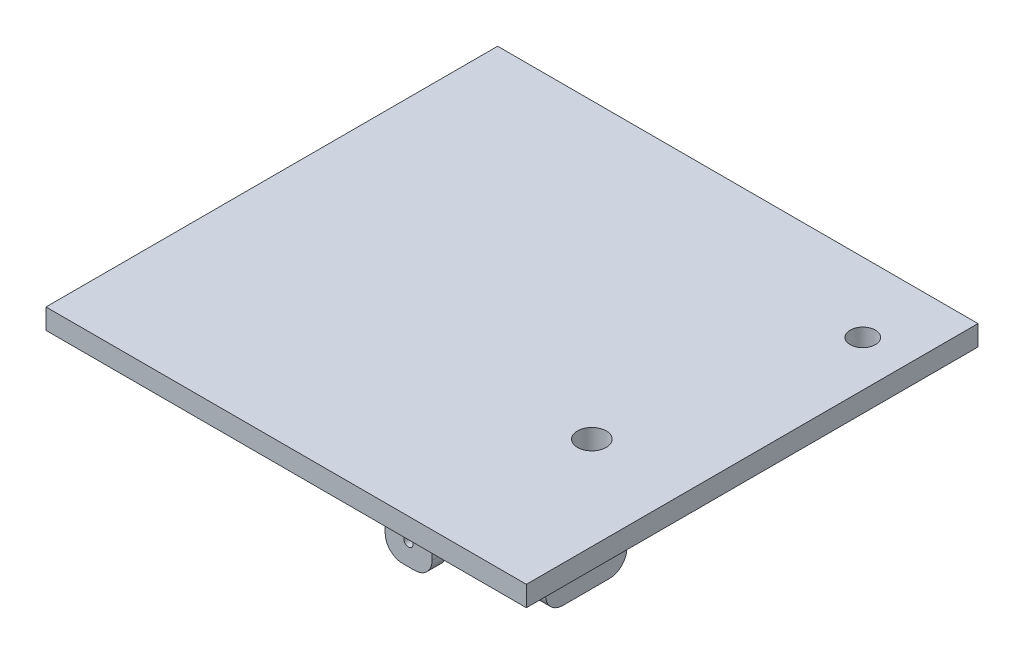
SolidWorks part; units mm, degrees
ref_plane "Front Plane" through (0, 0, 0) normal (0, 0, 1) x (1, 0, 0)
ref_plane "Top Plane" through (0, 0, 0) normal (0, 1, 0) x (1, 0, 0)
ref_plane "Right Plane" through (0, 0, 0) normal (1, 0, 0) x (0, 0, -1)
sketch "Sketch2" plane through (0, 0, 0) normal (0, 1, 0) x (1, 0, 0)
  line L0 (0, 0) -> (0, 77.75)
  line L1 (0, 77.75) -> (82.7, 77.75)
  line L2 (82.7, 77.75) -> (82.7, 0)
  line L3 (82.7, 0) -> (0, 0)
  dimension "D1" = 77.75
  dimension "D2" = 82.7
extrude "Boss-Extrude1" add sketch "Sketch2" along normal blind 3.5
sketch "Sketch3" plane through (0, 3.5, 0) normal (0, 1, 0) x (1, 0, 0)
  line L0 (54.7, 73.05) -> (44.7, 73.05)
  line L1 (44.7, 73.05) -> (44.7, 70.55)
  line L2 (44.7, 70.55) -> (54.7, 70.55)
  line L3 (54.7, 70.55) -> (54.7, 73.05)
  line L4 (82.7, 77.75) -> (0, 77.75) construction
  line L5 (82.7, 0) -> (82.7, 77.75) construction
  line L6 (61.77, 4.7) -> (51.7, 4.7)
  line L7 (51.7, 4.7) -> (51.7, 7.2)
  line L8 (51.7, 7.2) -> (61.77, 7.2)
  line L9 (61.77, 7.2) -> (61.77, 4.7)
  line L10 (0, 0) -> (82.7, 0) construction
  line L11 (75.5, 8) -> (75.5, 22)
  line L12 (75.5, 22) -> (78, 22)
  line L13 (78, 22) -> (78, 8)
  line L14 (78, 8) -> (75.5, 8)
  point P6 (54.7, 71.8)
  dimension "D1" = 4.7
  dimension "D2" = 28
  dimension "D3" = 38
  dimension "D4" = 4.7
  dimension "D5" = 2.5
  dimension "D6" = 2.5
  dimension "D7" = 31
  dimension "D8" = 20.93
  dimension "D9" = 4.7
  dimension "D10" = 2.5
  dimension "D11" = 8
  dimension "D12" = 22
extrude "Boss-Extrude2" add sketch "Sketch3" against normal blind 12.25
sketch "Sketch4" plane through (0, 0, 0) normal (0, -1, 0) x (1, 0, 0)
  line L0 (60.7, -29.75) -> (72.7, -29.75) construction
  line L1 (82.7, -77.75) -> (0, -77.75) construction
  line L3 (62.7, -30.275) -> (62.7, -24.275)
  line L4 (62.7, -30.275) -> (70.7, -30.275)
  line L5 (70.7, -30.275) -> (70.7, -24.275)
  line L7 (70.7, -24.275) -> (62.7, -24.275)
  line L8 (3.65, -5) -> (3.65, -72.75)
  line L9 (3.65, -72.75) -> (5.65, -72.75)
  line L10 (5.65, -72.75) -> (5.65, -5)
  line L11 (5.65, -5) -> (3.65, -5)
  line L12 (0, -77.75) -> (0, 0) construction
  line L13 (0, 0) -> (82.7, 0) construction
  line L14 (82.7, 0) -> (82.7, -77.75) construction
  circle A1 centre (66.7, -27.275) radius 2.475
  dimension "D2" = 48
  dimension "D3" = 20
  dimension "D4" = 4
  dimension "D5" = 4
  dimension "D6" = 53.475
  dimension "D8" = 3
  dimension "D10" = 2
  dimension "D11" = 3.65
  dimension "D12" = 5
  dimension "D13" = 5
extrude "Boss-Extrude3" add sketch "Sketch4" along normal blind 2.3 contours L4 L5 L7 L3
draft "Draft1" type of draft neutral plane draft angle 50 faces to draft 4 face at (70.7, -1.15, -27.275) face at (62.7, -1.15, -27.275) face at (66.7, -1.15, -24.275) face at (66.7, -1.15, -30.275) neutral plane through (0, -2.3, 0) neutral plane normal (0, -1, 0) parameters "D1"=50
extrude "Cut-Extrude1" cut sketch "Sketch4<3>" against normal up to surface and the other way up to surface contours A1 up to face at (41.35, 3.5, -38.875) other way up to face at (66.7, -2.3, -27.275)
sketch "Sketch4<3>" plane through (0, 0, 0) normal (0, -1, 0) x (1, 0, 0) same geometry as "Sketch4"
extrude "Boss-Extrude4" add sketch "Sketch4<4>" along normal blind 4 contours L10 L11 L8 L9
sketch "Sketch4<4>" plane through (0, 0, 0) normal (0, -1, 0) x (1, 0, 0) same geometry as "Sketch4"
sketch "Sketch5" plane through (0, 0, 0) normal (0, -1, 0) x (1, 0, 0)
  line L0 (82.7, -77.75) -> (0, -77.75) construction
  line L3 (82.7, 0) -> (82.7, -77.75) construction
  circle A0 centre (74.84, -65.77) radius 2.175
  dimension "D1" = 4.35
  dimension "D2" = 11.98
  dimension "D3" = 7.86
extrude "Cut-Extrude2" cut sketch "Sketch5" against normal up to surface (3.5 mm away) up to face at (66.7, 3.5, -29.75)
sketch "Sketch6" plane through (0, 0, -4.7) normal (0, 0, 1) x (1, 0, 0)
  line L0 (0, 0) -> (82.7, 0) construction
  line L1 (82.7, 3.5) -> (82.7, 0) construction
  circle A0 centre (57.7, -5) radius 0.8
  dimension "D1" = 1.6
  dimension "D2" = 5
  dimension "D3" = 25
extrude "Cut-Extrude3" cut sketch "Sketch6" against normal up to surface (2.5 mm away) up to face at (56.735, -4.375, -7.2)
sketch "Sketch7" plane through (0, 0, -73.05) normal (0, 0, -1) x (-1, 0, 0)
  line L0 (-82.7, 0) -> (0, 0) construction
  line L1 (-82.7, 3.5) -> (-82.7, 0) construction
  circle A0 centre (-49.7, -5) radius 0.8
  point P6 (-82.7, 1.75)
  dimension "D2" = 1.6
  dimension "D1" = 5
  dimension "D3" = 33
extrude "Cut-Extrude4" cut sketch "Sketch7" against normal up to surface (2.5 mm away) up to face at (49.7, -4.375, -70.55)
sketch "Sketch9" plane through (0, 0, -4.7) normal (0, 0, 1) x (1, 0, 0)
  line L0 (53.7, 0) -> (53.7, -8.75)
  line L1 (61.77, 0) -> (51.7, 0) construction
  line L2 (51.7, -8.75) -> (61.77, -8.75) construction
  line L3 (53.7, -8.75) -> (51.7, -8.75)
  line L4 (51.7, -8.75) -> (51.7, 0)
  line L5 (51.7, 0) -> (53.7, 0)
  dimension "D1" = 2
extrude "Cut-Extrude5" cut sketch "Sketch9" against normal blind 4
fillet "Fillet1" radius 5 2 edges at (54.7, -8.75, -71.8) (44.7, -8.75, -71.8)
fillet "Fillet4" radius 1 1 edges at (5.65, 0, -38.875)
fillet "Fillet5" radius 0.5 1 edges at (5.65, -4, -38.875)
sketch "Sketch10" plane through (78, 0, 0) normal (1, 0, 0) x (0, 0, -1)
  line L0 (8, -4.375) -> (22, -4.375) construction
  line L1 (8, -8.75) -> (8, 0) construction
  line L2 (22, -8.75) -> (22, 0) construction
  line L5 (0, 0) -> (77.75, 0) construction
  line L6 (0, 3.5) -> (0, 0) construction
  circle A0 centre (15, -3.5) radius 0.8
  dimension "D2" = 1.6
  dimension "D1" = 3.5
  dimension "D3" = 15
extrude "Cut-Extrude6" cut sketch "Sketch10" against normal up to surface (2.5 mm away) up to face at (75.5, -4.375, -15)
sketch "Sketch13" plane through (0, 0, -8) normal (0, 0, 1) x (1, 0, 0)
  line L0 (78, -8.75) -> (78, -7.5)
  line L1 (78, -8.75) -> (78, 0) construction
  line L2 (78, -7.5) -> (75.5, -7.5)
  line L3 (75.5, -8.75) -> (75.5, 0) construction
  line L4 (75.5, -7.5) -> (75.5, -8.75)
  line L5 (75.5, -8.75) -> (78, -8.75) construction
  line L6 (75.5, -8.75) -> (78, -8.75)
  dimension "D1" = 1.25
extrude "Cut-Extrude7" cut sketch "Sketch13" against normal up to surface (14 mm away) up to face at (76.75, -4.375, -22)
fillet "Fillet6" radius 3 2 edges at (76.75, -7.5, -8) (76.75, -7.5, -22)
fillet "Fillet7" radius 3 2 edges at (53.7, -8.75, -5.95) (61.77, -8.75, -5.95)
